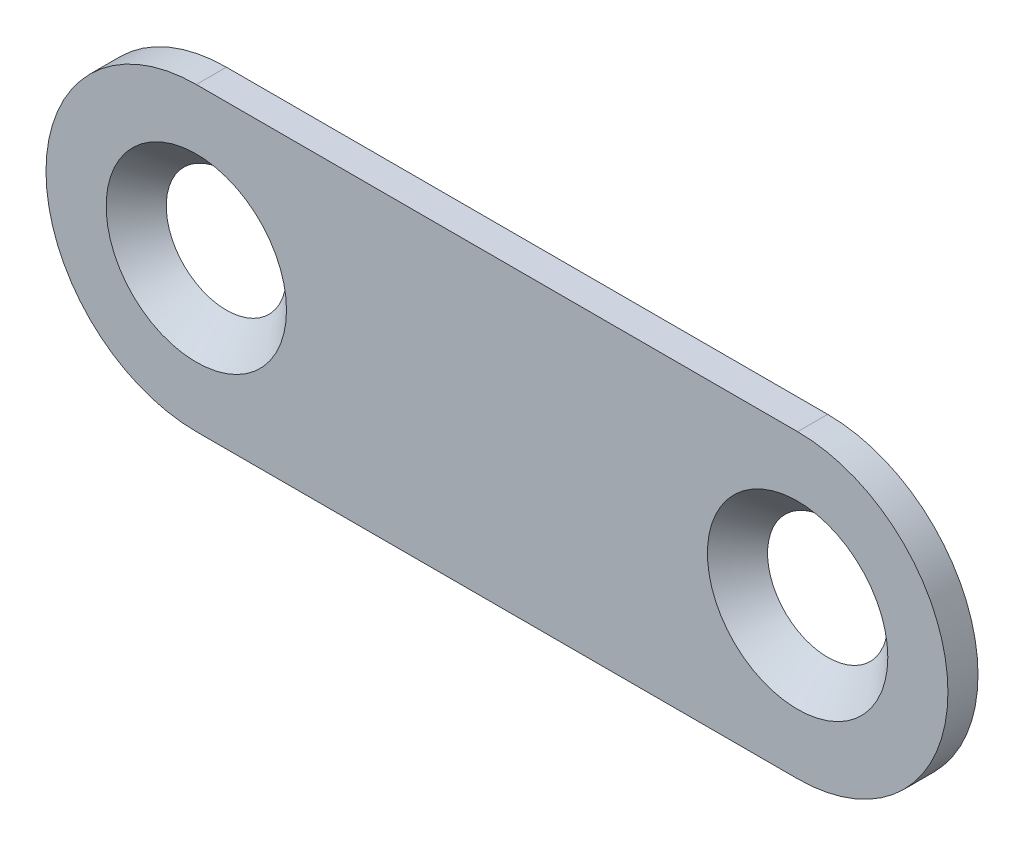
SolidWorks part; units mm, degrees
ref_plane "Plan de face" through (0, 0, 0) normal (0, 0, 1) x (1, 0, 0)
ref_plane "Plan de dessus" through (0, 0, 0) normal (0, 1, 0) x (1, 0, 0)
ref_plane "Plan de droite" through (0, 0, 0) normal (1, 0, 0) x (0, 0, -1)
sketch "Esquisse1" plane through (0, 0, 0) normal (0, 0, 1) x (1, 0, 0)
  line L1 (0, 0) -> (20, 0)
  line L2 (0, 0) -> (0, -10)
  line L3 (0, -10) -> (20, -10)
  line L4 (20, 0) -> (20, -10)
  arc A0 (20, 0) -> (20, -10) centre (20, -5) cw
  arc A1 (0, 0) -> (0, -10) centre (0, -5) ccw
  circle A2 centre (0, -5) radius 2
  circle A3 centre (20, -5) radius 2
  point P11 (-5, -5)
  point P12 (25, -5)
  dimension "D5" = 4
  dimension "D6" = 4
  dimension "D1" = 30
  dimension "D3" = 5
  dimension "D4" = 5
  dimension "D7" = 10
extrude "Boss.-Extru.1" add sketch "Esquisse1" along normal blind 1 contours L4 L1 L2 L3 A3 A2 | A0 L4 | L2 A1 region at (10, -5, 0) region at (-2.3646, -5, 0) region at (22.3646, -5, 0)
chamfer "Chanfrein1" distance 1 angle 45 2 edges at (22, -5, 1) (2, -5, 1)
